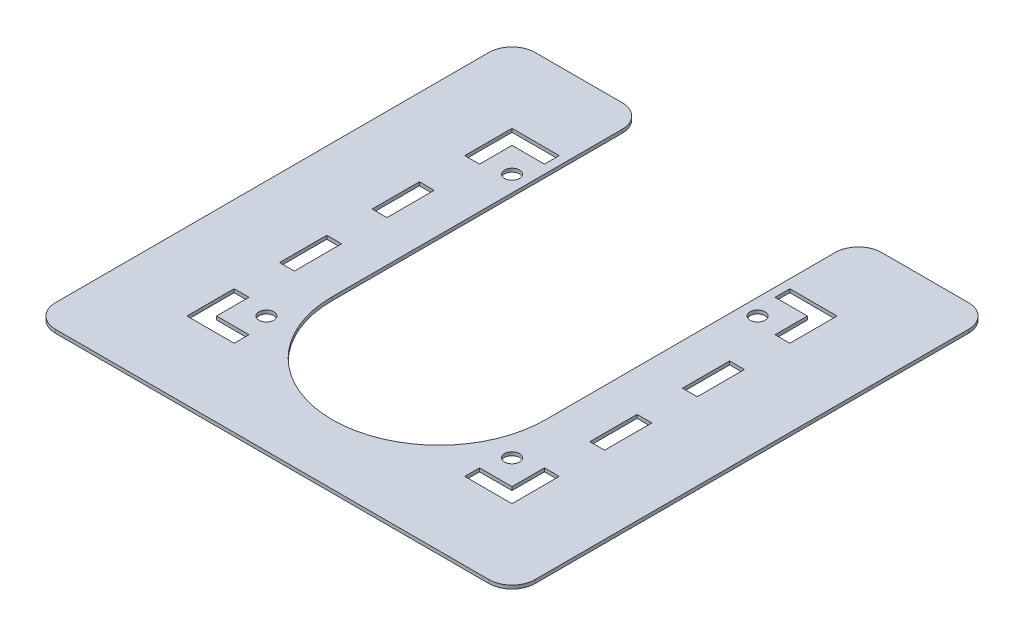
SolidWorks part; units mm, degrees
ref_plane "Front Plane" through (0, 0, 0) normal (0, 0, 1) x (1, 0, 0)
ref_plane "Top Plane" through (0, 0, 0) normal (0, 1, 0) x (1, 0, 0)
ref_plane "Right Plane" through (0, 0, 0) normal (1, 0, 0) x (0, 0, -1)
sketch "Sketch1" plane through (0, 0, 0) normal (0, 1, 0) x (1, 0, 0)
  line L0 (0, 0) -> (0, 21) construction
  line L1 (51.8722, -39.9014) -> (51.8722, 63.843) construction
  line L3 (51.8722, 63.843) -> (-51.8722, 63.843) construction
  line L4 (-51.8722, 63.843) -> (-51.8722, -39.9014) construction
  line L5 (51.8722, -34.9014) -> (51.8722, 58.843)
  line L6 (-46.8722, -39.9014) -> (46.8722, -39.9014)
  line L7 (51.8722, 63.843) -> (-51.8722, 63.843) construction
  line L8 (-51.8722, 58.843) -> (-51.8722, -34.9014)
  line L10 (36.8722, -39.9014) -> (36.8722, 63.843) construction
  line L11 (-36.8722, -39.9014) -> (-36.8722, 63.843) construction
  line L12 (36.8722, -39.9014) -> (36.8722, 63.843) construction
  line L13 (-36.8722, -39.9014) -> (-36.8722, 63.843) construction
  line L14 (23.0585, -3.843) -> (23.0585, 58.843)
  line L15 (-23.0585, -3.843) -> (-23.0585, 58.843)
  line L16 (-46.8722, 63.843) -> (-28.0585, 63.843)
  line L17 (28.0585, 63.843) -> (46.8722, 63.843)
  circle A0 centre (0, 0) radius 21 construction
  circle A1 centre (0, 0) radius 21 construction
  circle A2 centre (26.5585, -14.5877) radius 1.6 construction
  circle A3 centre (-26.5585, -14.5877) radius 1.6 construction
  circle A4 centre (26.5585, 38.5292) radius 1.6 construction
  circle A5 centre (-26.5585, 38.5292) radius 1.6 construction
  circle A6 centre (26.5585, -14.5877) radius 1.6
  circle A7 centre (-26.5585, -14.5877) radius 1.6
  circle A8 centre (26.5585, 38.5292) radius 1.6
  circle A9 centre (-26.5585, 38.5292) radius 1.6
  circle A10 centre (0, -3.843) radius 21.0585 construction
  arc A11 (-21.0585, -3.843) -> (21.0585, -3.843) centre (0, -3.843) ccw construction
  arc A12 (-23.0585, -3.843) -> (23.0585, -3.843) centre (0, -3.843) ccw
  arc A13 (28.0585, 63.843) -> (23.0585, 58.843) centre (28.0585, 58.843) ccw
  circle A14 centre (0, -3.843) radius 23.0585 construction
  arc A15 (-28.0585, 63.843) -> (-23.0585, 58.843) centre (-28.0585, 58.843) cw
  arc A16 (46.8722, 63.843) -> (51.8722, 58.843) centre (46.8722, 58.843) cw
  arc A17 (51.8722, -34.9014) -> (46.8722, -39.9014) centre (46.8722, -34.9014) cw
  arc A18 (-46.8722, -39.9014) -> (-51.8722, -34.9014) centre (-46.8722, -34.9014) cw
  arc A19 (-51.8722, 58.843) -> (-46.8722, 63.843) centre (-46.8722, 58.843) cw
  point P39 (31.0585, -3.843)
  point P42 (23.0585, 63.843)
  point P45 (-23.0585, 63.843)
  dimension "D1" = 2
  dimension "D2" = 5
sketch "Sketch2" plane through (0, 0, 0) normal (0, 0, 1) x (1, 0, 0)
  line L1 (51.8722, -0.75) -> (-51.8722, -0.75)
  line L2 (51.8722, -0.75) -> (51.8722, 0)
  line L3 (51.8722, 0) -> (-51.8722, 0)
  line L4 (-51.8722, -0.75) -> (-51.8722, 0)
extrude "Boss-Extrude1" add sketch "Sketch1" against normal up to vertex (0.75 mm away) up to point (51.8722, -0.75, 0)
sketch "Sketch3" plane through (0, 0, 0) normal (0, 1, 0) x (1, 0, 0)
  line L4 (31.9585, -3.1543) -> (35.1585, -3.1543)
  line L5 (31.9585, 7.0624) -> (31.9585, -3.1543)
  line L6 (35.1585, 7.0624) -> (31.9585, 7.0624)
  line L7 (35.1585, -3.1543) -> (35.1585, 7.0624)
  line L8 (31.9585, -3.1543) -> (35.1585, -3.1543)
  line L9 (31.9585, 7.0624) -> (31.9585, -3.1543)
  line L10 (35.1585, 7.0624) -> (31.9585, 7.0624)
  line L11 (35.1585, -3.1543) -> (35.1585, 7.0624)
  line L12 (35.1585, 16.8791) -> (35.1585, 27.0958)
  line L13 (31.9585, 16.8791) -> (35.1585, 16.8791)
  line L14 (35.1585, 36.9125) -> (35.1585, 47.1292)
  line L15 (35.1585, 47.1292) -> (24.9418, 47.1292)
  line L16 (24.9418, 47.1292) -> (24.9418, 43.9292)
  line L17 (24.9418, 43.9292) -> (31.9585, 43.9292)
  line L18 (31.9585, 43.9292) -> (31.9585, 36.9125)
  line L19 (31.9585, 36.9125) -> (35.1585, 36.9125)
  line L20 (35.1585, 36.9125) -> (35.1585, 47.1292)
  line L21 (35.1585, 47.1292) -> (24.9418, 47.1292)
  line L22 (24.9418, 47.1292) -> (24.9418, 43.9292)
  line L23 (24.9418, 43.9292) -> (31.9585, 43.9292)
  line L24 (31.9585, 43.9292) -> (31.9585, 36.9125)
  line L25 (31.9585, 36.9125) -> (35.1585, 36.9125)
  line L26 (31.9585, 27.0958) -> (31.9585, 16.8791)
  line L27 (35.1585, 27.0958) -> (31.9585, 27.0958)
  line L28 (35.1585, 16.8791) -> (35.1585, 27.0958)
  line L29 (31.9585, 16.8791) -> (35.1585, 16.8791)
  line L30 (31.9585, 27.0958) -> (31.9585, 16.8791)
  line L31 (35.1585, 27.0958) -> (31.9585, 27.0958)
  line L32 (-35.1585, 27.0958) -> (-35.1585, 16.8791)
  line L33 (-35.1585, 16.8791) -> (-31.9585, 16.8791)
  line L34 (-31.9585, 16.8791) -> (-31.9585, 27.0958)
  line L35 (-31.9585, 27.0958) -> (-35.1585, 27.0958)
  line L36 (-35.1585, 27.0958) -> (-35.1585, 16.8791)
  line L37 (-35.1585, 16.8791) -> (-31.9585, 16.8791)
  line L38 (-31.9585, 16.8791) -> (-31.9585, 27.0958)
  line L39 (-31.9585, 27.0958) -> (-35.1585, 27.0958)
  line L40 (-31.9585, 7.0624) -> (-35.1585, 7.0624)
  line L41 (-35.1585, 7.0624) -> (-35.1585, -3.1543)
  line L42 (-31.9585, 36.9125) -> (-31.9585, 43.9292)
  line L43 (-35.1585, 36.9125) -> (-31.9585, 36.9125)
  line L44 (-35.1585, 47.1292) -> (-35.1585, 36.9125)
  line L45 (-24.9418, 47.1292) -> (-35.1585, 47.1292)
  line L46 (-24.9418, 43.9292) -> (-24.9418, 47.1292)
  line L47 (-31.9585, 43.9292) -> (-24.9418, 43.9292)
  line L48 (-31.9585, 36.9125) -> (-31.9585, 43.9292)
  line L49 (-35.1585, 36.9125) -> (-31.9585, 36.9125)
  line L50 (-35.1585, 47.1292) -> (-35.1585, 36.9125)
  line L51 (-24.9418, 47.1292) -> (-35.1585, 47.1292)
  line L52 (-24.9418, 43.9292) -> (-24.9418, 47.1292)
  line L53 (-31.9585, 43.9292) -> (-24.9418, 43.9292)
  line L54 (31.9585, -12.971) -> (31.9585, -19.9877)
  line L55 (35.1585, -12.971) -> (31.9585, -12.971)
  line L56 (35.1585, -23.1877) -> (35.1585, -12.971)
  line L57 (24.9418, -23.1877) -> (35.1585, -23.1877)
  line L58 (24.9418, -19.9877) -> (24.9418, -23.1877)
  line L59 (31.9585, -19.9877) -> (24.9418, -19.9877)
  line L60 (31.9585, -12.971) -> (31.9585, -19.9877)
  line L61 (35.1585, -12.971) -> (31.9585, -12.971)
  line L62 (35.1585, -23.1877) -> (35.1585, -12.971)
  line L63 (24.9418, -23.1877) -> (35.1585, -23.1877)
  line L64 (24.9418, -19.9877) -> (24.9418, -23.1877)
  line L65 (31.9585, -19.9877) -> (24.9418, -19.9877)
  line L66 (-35.1585, -12.971) -> (-35.1585, -23.1877)
  line L67 (-35.1585, -23.1877) -> (-24.9418, -23.1877)
  line L68 (-24.9418, -23.1877) -> (-24.9418, -19.9877)
  line L69 (-24.9418, -19.9877) -> (-31.9585, -19.9877)
  line L70 (-31.9585, -19.9877) -> (-31.9585, -12.971)
  line L71 (-31.9585, -12.971) -> (-35.1585, -12.971)
  line L72 (-35.1585, -12.971) -> (-35.1585, -23.1877)
  line L73 (-35.1585, -23.1877) -> (-24.9418, -23.1877)
  line L74 (-24.9418, -23.1877) -> (-24.9418, -19.9877)
  line L75 (-24.9418, -19.9877) -> (-31.9585, -19.9877)
  line L76 (-31.9585, -19.9877) -> (-31.9585, -12.971)
  line L77 (-31.9585, -12.971) -> (-35.1585, -12.971)
  line L78 (-35.1585, -3.1543) -> (-31.9585, -3.1543)
  line L79 (-31.9585, -3.1543) -> (-31.9585, 7.0624)
  line L80 (-31.9585, 7.0624) -> (-35.1585, 7.0624)
  line L81 (-35.1585, 7.0624) -> (-35.1585, -3.1543)
  line L82 (-35.1585, -3.1543) -> (-31.9585, -3.1543)
  line L83 (-31.9585, -3.1543) -> (-31.9585, 7.0624)
  dimension "D1" = 0
  dimension "D2" = 0
  dimension "D3" = 0
  dimension "D4" = 0
  dimension "D5" = 0
  dimension "D6" = 0
  dimension "D7" = 0
  dimension "D8" = 0
extrude "Cut-Extrude1" cut sketch "Sketch3" against normal through all
sketch "Sketch4" [suppressed] plane through (0, 0, 0) normal (0, 1, 0) x (1, 0, 0)
  line L4 (5.1, -36.8014) -> (-5.1, -36.8014)
  line L5 (-5.1, -36.8014) -> (-5.1, -40.0014)
  line L6 (-5.1, -40.0014) -> (5.1, -40.0014)
  line L7 (5.1, -40.0014) -> (5.1, -36.8014)
  line L8 (5.1, -36.8014) -> (-5.1, -36.8014)
  line L9 (-5.1, -36.8014) -> (-5.1, -40.0014)
  line L10 (-5.1, -40.0014) -> (5.1, -40.0014)
  line L11 (5.1, -40.0014) -> (5.1, -36.8014)
  line L12 (25.1, -36.8014) -> (14.9, -36.8014)
  line L13 (14.9, -36.8014) -> (14.9, -40.0014)
  line L14 (14.9, -40.0014) -> (25.1, -40.0014)
  line L15 (25.1, -40.0014) -> (25.1, -36.8014)
  line L16 (25.1, -36.8014) -> (14.9, -36.8014)
  line L17 (14.9, -36.8014) -> (14.9, -40.0014)
  line L18 (14.9, -40.0014) -> (25.1, -40.0014)
  line L19 (25.1, -40.0014) -> (25.1, -36.8014)
  line L20 (34.9722, -24.8014) -> (31.7722, -24.8014)
  line L21 (34.9722, -35.0014) -> (34.9722, -24.8014)
  line L22 (31.7722, -35.0014) -> (34.9722, -35.0014)
  line L23 (31.7722, -24.8014) -> (31.7722, -35.0014)
  line L24 (34.9722, -24.8014) -> (31.7722, -24.8014)
  line L25 (34.9722, -35.0014) -> (34.9722, -24.8014)
  line L26 (31.7722, -35.0014) -> (34.9722, -35.0014)
  line L27 (31.7722, -24.8014) -> (31.7722, -35.0014)
  line L28 (31.7722, 48.743) -> (34.9722, 48.743)
  line L29 (31.7722, 58.943) -> (31.7722, 48.743)
  line L30 (34.9722, 58.943) -> (31.7722, 58.943)
  line L31 (34.9722, 48.743) -> (34.9722, 58.943)
  line L32 (31.7722, 48.743) -> (34.9722, 48.743)
  line L33 (31.7722, 58.943) -> (31.7722, 48.743)
  line L34 (34.9722, 58.943) -> (31.7722, 58.943)
  line L35 (34.9722, 48.743) -> (34.9722, 58.943)
  line L36 (-25.1, -40.0014) -> (-14.9, -40.0014)
  line L37 (-14.9, -40.0014) -> (-14.9, -36.8014)
  line L38 (-14.9, -36.8014) -> (-25.1, -36.8014)
  line L39 (-25.1, -36.8014) -> (-25.1, -40.0014)
  line L40 (-25.1, -40.0014) -> (-14.9, -40.0014)
  line L41 (-14.9, -40.0014) -> (-14.9, -36.8014)
  line L42 (-14.9, -36.8014) -> (-25.1, -36.8014)
  line L43 (-25.1, -36.8014) -> (-25.1, -40.0014)
  dimension "D1" = 0
  dimension "D2" = 0
  dimension "D3" = 0
  dimension "D4" = 0
  dimension "D5" = 0
extrude "Cut-Extrude2" [suppressed] cut sketch "Sketch4" against normal through all
